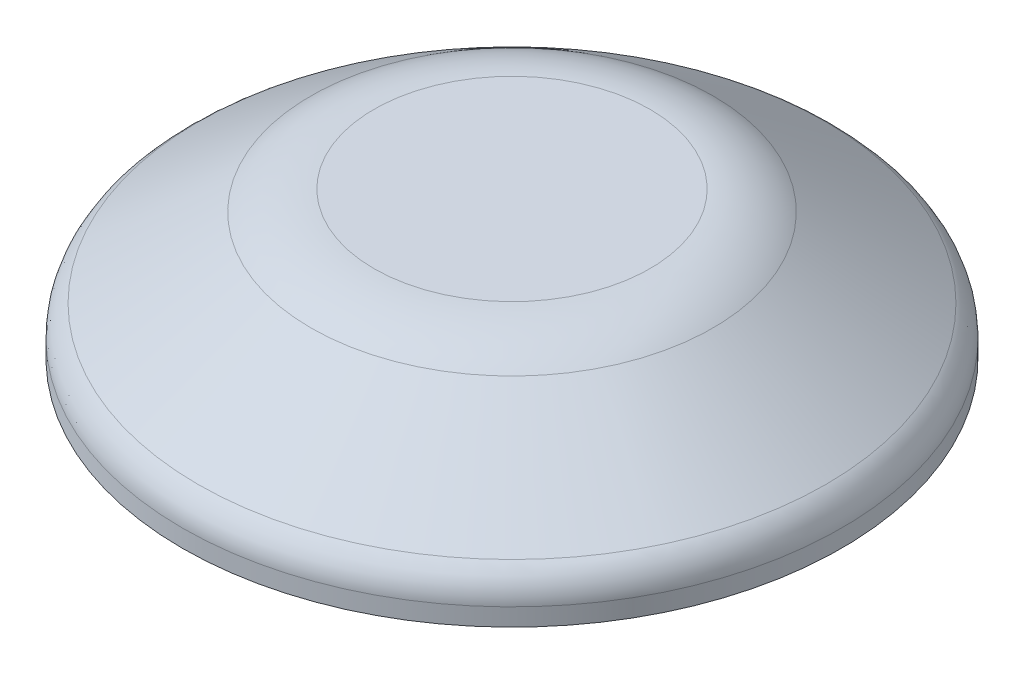
SolidWorks part; units mm, degrees
material "ABS"
ref_plane "Front Plane" through (0, 0, 0) normal (0, 0, 1) x (1, 0, 0)
ref_plane "Top Plane" through (0, 0, 0) normal (0, 1, 0) x (1, 0, 0)
ref_plane "Right Plane" through (0, 0, 0) normal (1, 0, 0) x (0, 0, -1)
sketch "Sketch1" plane through (0, 0, 0) normal (0, 1, 0) x (1, 0, 0)
  circle A0 centre (0, 0) radius 9
  dimension "D1" = 18
extrude "Boss-Extrude1" add sketch "Sketch1" along normal blind 4
sketch "Sketch2" plane through (0, 0, 0) normal (0, -1, 0) x (1, 0, 0)
  line L0 (0, 0) -> (0, 5.3059) construction
  line L2 (1.55, 6.1059) -> (-1.55, 6.1059)
  line L3 (1.55, 6.1059) -> (1.55, 4.5059)
  line L5 (-1.55, 6.1059) -> (-1.55, 4.5059)
  line L6 (1.55, 6.1059) -> (-1.55, 4.5059) construction
  line L7 (1.55, 4.5059) -> (-1.55, 6.1059) construction
  arc A0 (-1.55, 4.5059) -> (1.55, 4.5059) centre (0, 0) ccw
  dimension "D1" = 9.53
  dimension "D2" = 3.1
  dimension "D3" = 1.6
extrude "Cut-Extrude1" cut sketch "Sketch2" against normal blind 1.1
sketch "Sketch3" plane through (0, 1.1, 0) normal (0, -1, 0) x (1, 0, 0)
  circle A0 centre (0, 0) radius 4.765
extrude "Cut-Extrude2" cut sketch "Sketch3" against normal blind 2
chamfer "Chamfer1" distance 3 angle 55 1 edges at (0, 4, 9) first distance on face at (0, 4, 9)
fillet "Fillet1" radius 1 1 edges at (0, 1, 9)
fillet "Fillet2" radius 3 1 edges at (0, 4, 4.7156)
chamfer "Chamfer2" distance 0.25 angle 45 4 edges at (0, 0, -4.765) (1.55, 0, 5.3059) (0, 0, 6.1059) (-1.55, 0, 5.3059)
fillet "Fillet3" radius 0.25 7 edges at (0, 1.1, 6.1059) (0, 3.1, -4.765)
